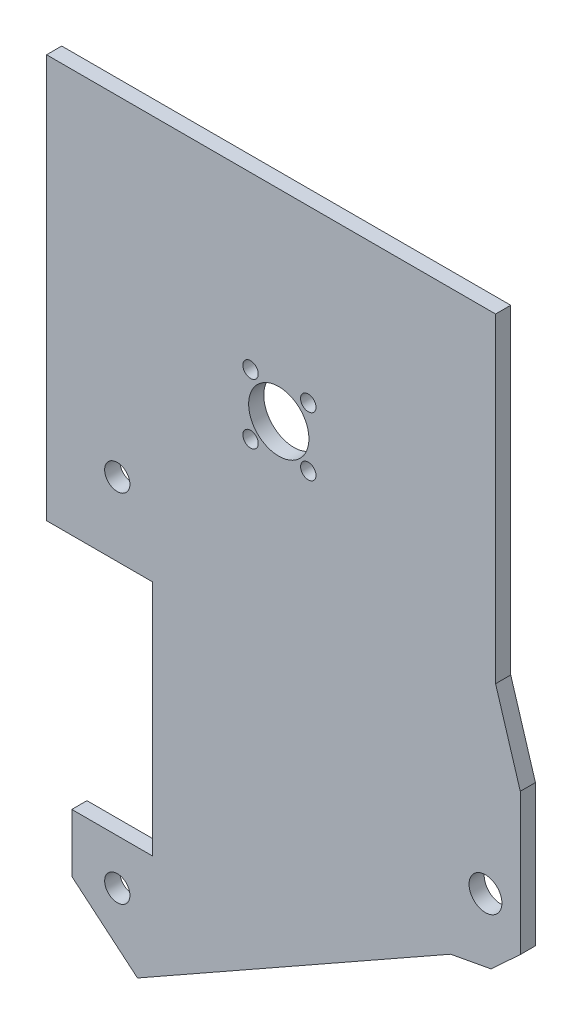
SolidWorks part; units mm, degrees
ref_plane "Front Plane" through (0, 0, 0) normal (0, 0, 1) x (1, 0, 0)
ref_plane "Top Plane" through (0, 0, 0) normal (0, 1, 0) x (1, 0, 0)
ref_plane "Right Plane" through (0, 0, 0) normal (1, 0, 0) x (0, 0, -1)
sketch "Sketch1" plane through (0, 0, 0) normal (0, 0, 1) x (1, 0, 0)
  line L0 (0, 0) -> (88.9, 0)
  line L1 (88.9, 0) -> (88.9, -3.5)
  line L2 (88.9, -3.5) -> (93.7917, -19.5)
  line L3 (93.7917, -19.5) -> (93.7917, -47.5)
  line L4 (0, 0) -> (0, -20)
  line L5 (0, -20) -> (21, -20)
  line L6 (21, -20) -> (21, -67)
  line L7 (21, -67) -> (5, -67)
  line L8 (5, -67) -> (5, -78.5)
  line L9 (5, -78.5) -> (18, -89.4083)
  line L10 (18, -89.4083) -> (80, -54.3304)
  line L11 (80, -54.3304) -> (88, -52.8477)
  line L12 (88, -52.8477) -> (93.7917, -47.5)
  dimension "D1" = 88.9
  dimension "D2" = 3.5
  dimension "D3" = 163
  dimension "D4" = 16
  dimension "D5" = 28
  dimension "D6" = 20
  dimension "D7" = 21
  dimension "D8" = 47
  dimension "D9" = 16
  dimension "D10" = 11.5
  dimension "D11" = 130
  dimension "D12" = 13
  dimension "D13" = 110.5
  dimension "D14" = 62
  dimension "D15" = 8
  dimension "D16" = 161
extrude "Boss-Extrude1" add sketch "Sketch1" along normal blind 3
sketch "Sketch2" plane through (0, 0, 0) normal (0, 1, 0) x (1, 0, 0)
  line L0 (45.8978, 14) -> (40.3978, 14) construction
  line L1 (0, -3) -> (88.9, -3)
  line L2 (0, -3) -> (0, 54)
  line L3 (0, 54) -> (88.9, 54)
  line L4 (88.9, -3) -> (88.9, 54)
  circle A0 centre (40.3978, 8.5) radius 1.5
  circle A1 centre (40.3978, 20) radius 1.5
  circle A2 centre (51.8978, 8.5) radius 1.5
  circle A3 centre (51.8978, 20) radius 1.5
  ellipse E0 centre (45.8978, 14) end of major axis (45.8978, 8) minor radius 5.5
  dimension "D9" = 3
  dimension "D10" = 3
  dimension "D11" = 3
  dimension "D12" = 3
  dimension "D1" = 88.9
  dimension "D2" = 57
  dimension "D3" = 45.8978
  dimension "D4" = 5.5
  dimension "D5" = 11.5
  dimension "D6" = 23
  dimension "D7" = 11.5
  dimension "D8" = 17
  dimension "D13" = 12
  dimension "D14" = 11
extrude "Boss-Extrude2" add sketch "Sketch2" along normal blind 3
ref_plane "Plane1" through (85.9, 0, 0) normal (1, 0, 0) x (0, 0, -1)
sketch "Sketch3" plane through (85.9, 0, 0) normal (1, 0, 0) x (0, 0, -1)
  line L0 (11.5, 0) -> (0, 0)
  line L1 (0, 0) -> (54, 0) construction
  line L2 (0, 0) -> (0, -11.5)
  line L3 (0, -19.5) -> (0, -3.5) construction
  line L4 (0, -11.5) -> (11.5, 0)
  dimension "D1" = 11.5
  dimension "D2" = 11.5
extrude "Boss-Extrude3" add sketch "Sketch3" against normal blind 84.5
sketch "Sketch4" plane through (0, 0, 0) normal (0, 0, -1) x (-1, 0, 0)
  line L0 (-1.4, -11.5) -> (-85.9, -11.5) construction
  line L1 (-81.4, -11.5) -> (-6.4, -11.5)
  line L2 (-81.4, -11.5) -> (-81.4, 0)
  line L3 (-81.4, 0) -> (-6.4, 0)
  line L4 (-6.4, -11.5) -> (-6.4, 0)
  line L5 (-50.8976, 0) -> (-85.9, 0) construction
  line L6 (-85.9, 13.7659) -> (-85.9, -13.7659) construction
  dimension "D1" = 75
  dimension "D2" = 4.5
extrude "Cut-Extrude2" cut sketch "Sketch4" along normal blind 84.5
sketch "Sketch6" plane through (0, 0, 3) normal (0, 0, 1) x (1, 0, 0)
  line L0 (0, 3) -> (0, -20) construction
  line L1 (0, 3) -> (88.9, 3) construction
  circle A0 centre (14, -76) radius 2.5
  circle A1 centre (86.898, -40.5) radius 3.25
  circle A2 centre (14, -5.5) radius 2.5
  dimension "D1" = 5
  dimension "D2" = 5
  dimension "D3" = 6.5
  dimension "D4" = 14
  dimension "D5" = 8.5
  dimension "D6" = 79
  dimension "D7" = 14
  dimension "D8" = 43.5
  dimension "D9" = 72.898
extrude "Cut-Extrude3" cut sketch "Sketch6" against normal blind 84.5
sketch "Sketch7" plane through (0, 0, 0) normal (0, -1, 0) x (1, 0, 0)
  line L1 (88.9, -54) -> (0, -54)
  line L2 (88.9, -54) -> (88.9, 0)
  line L3 (88.9, 0) -> (0, 0)
  line L4 (0, -54) -> (0, 0)
extrude "Cut-Extrude4" cut sketch "Sketch7" against normal through all both and the other way through all
sketch "Sketch8" plane through (0, 0, 0) normal (0, 0, -1) x (-1, 0, 0)
  line L0 (-88.9, 3) -> (0, 3) construction
  line L1 (-88.9, 3) -> (0, 3)
  line L2 (-88.9, 3) -> (-88.9, 59.896)
  line L3 (-88.9, 59.896) -> (0, 59.896)
  line L4 (0, 3) -> (0, 59.896)
  line L5 (-45.974, 20.018) -> (-40.005, 20.018) construction
  circle A0 centre (-45.974, 20.018) radius 5.969
  circle A1 centre (-40.386, 26.114) radius 1.524
  circle A2 centre (-40.386, 14.176) radius 1.524
  circle A3 centre (-51.816, 26.114) radius 1.524
  circle A4 centre (-51.816, 14.43) radius 1.524
  point P17 (0, 0)
  point P18 (0, 0)
  dimension "D8" = 11.938
  dimension "D9" = 3.048
  dimension "D10" = 3.048
  dimension "D11" = 3.048
  dimension "D12" = 3.048
  dimension "D1" = 56.896
  dimension "D2" = 88.9
  dimension "D3" = 23.114
  dimension "D4" = 11.43
  dimension "D5" = 17.018
  dimension "D6" = 11.938
  dimension "D7" = 5.588
  dimension "D13" = 45.974
  dimension "D14" = 11.43
extrude "Boss-Extrude4" add sketch "Sketch8" against normal up to surface (3 mm away) up to face at (16.5, -76, 3)
